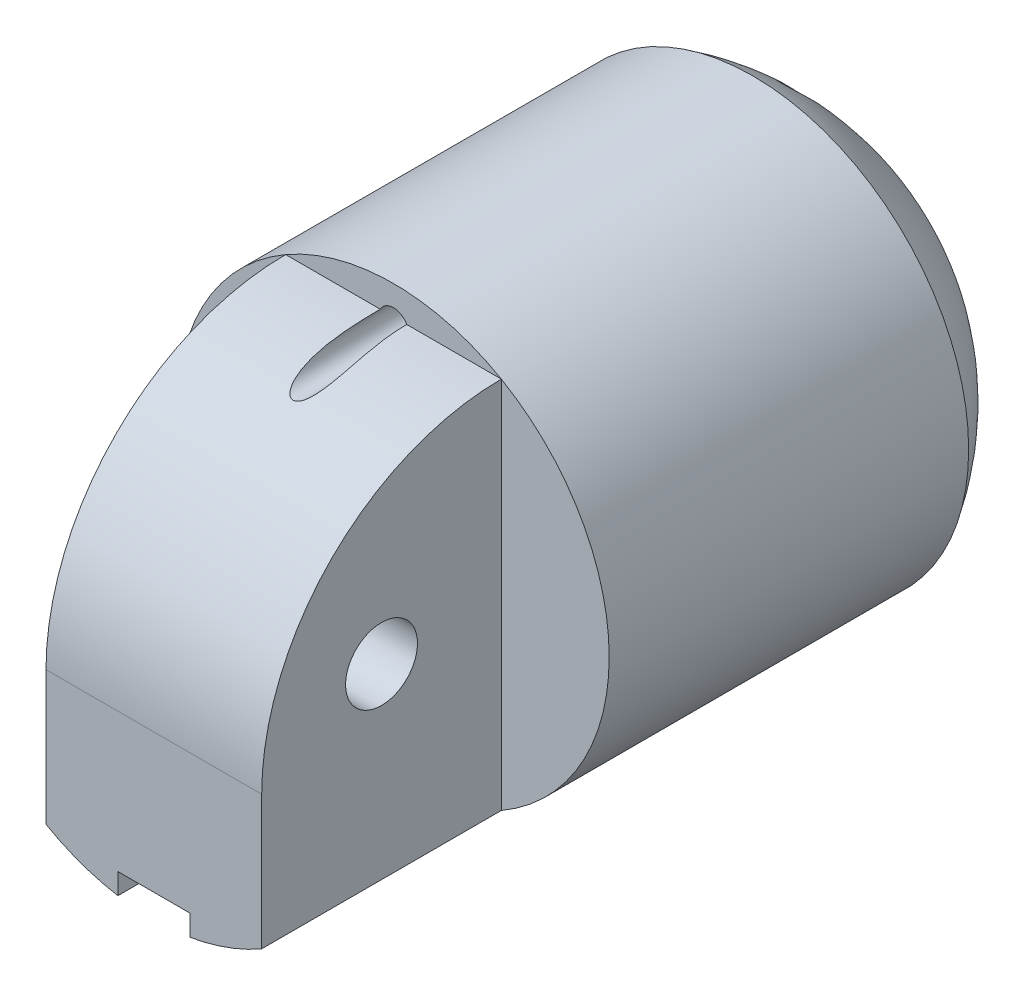
SolidWorks part; units mm, degrees
ref_plane "Front Plane" through (0, 0, 0) normal (0, 0, 1) x (1, 0, 0)
ref_plane "Top Plane" through (0, 0, 0) normal (0, 1, 0) x (1, 0, 0)
ref_plane "Right Plane" through (0, 0, 0) normal (1, 0, 0) x (0, 0, -1)
sketch "Sketch1" plane through (0, 0, 0) normal (0, 0, 1) x (1, 0, 0)
  circle A0 centre (0, 0) radius 9
extrude "Boss-Extrude1" add sketch "Sketch1" against normal blind 15
sketch "Sketch2" plane through (0, 0, 0) normal (0, 0, 1) x (1, 0, 0)
  line L0 (0, 9) -> (0, -9) construction
  line L1 (-4.5, 7.7942) -> (-4.5, -7.7942)
  line L2 (4.5, 7.7942) -> (4.5, -7.7942)
  line L3 (-4.5, 7.7942) -> (4.5, 7.7942)
  circle A0 centre (0, 0) radius 9 construction
  arc A1 (-4.5, -7.7942) -> (4.5, -7.7942) centre (0, 0) ccw
extrude "Boss-Extrude2" add sketch "Sketch2" along normal blind 10
dome "Dome2" faces to dome 1 distance 5 reverse direction no elliptical dome no face at (9, 0, -15) parameters "D1"=5
sketch "Sketch3" plane through (0, 0, 0) normal (1, 0, 0) x (0, 0, -1)
  circle A0 centre (-5, 0) radius 1.5
extrude "Cut-Extrude1" cut sketch "Sketch3" against normal through all both and the other way through all
fillet "Fillet4" radius 10 1 edges at (0, 7.7942, 10)
sketch "Sketch4" plane through (0, 0, 0) normal (0, 0, 1) x (1, 0, 0)
  circle A0 centre (0, 7.5) radius 0.625
  dimension "D1" = 1.25
extrude "Cut-Extrude2" cut sketch "Sketch4" against normal through all both and the other way through all
sketch "Sketch5" plane through (0, 0, 10) normal (0, 0, 1) x (1, 0, 0)
  line L1 (-1.5, -10) -> (1.5, -10)
  line L2 (-1.5, -10) -> (-1.5, -8)
  line L3 (-1.5, -8) -> (1.5, -8)
  line L4 (1.5, -10) -> (1.5, -8)
  line L5 (-1.5, -10) -> (1.5, -8) construction
  line L6 (-1.5, -8) -> (1.5, -10) construction
  arc A0 (-4.5, -7.7942) -> (4.5, -7.7942) centre (0, 0) ccw construction
  point P0 (0, -9)
  dimension "D1" = 2
  dimension "D2" = 3
extrude "Cut-Extrude3" cut sketch "Sketch5" against normal blind 20
sketch "Sketch6" plane through (0, -8, 0) normal (0, -1, 0) x (-1, 0, 0)
  line L0 (-1.5, 10) -> (1.5, 10) construction
  circle A0 centre (0, 7) radius 0.9
  point P4 (0, 10)
  dimension "D1" = 1.8
  dimension "D2" = 3
extrude "Cut-Extrude4" cut sketch "Sketch6" against normal blind 5
